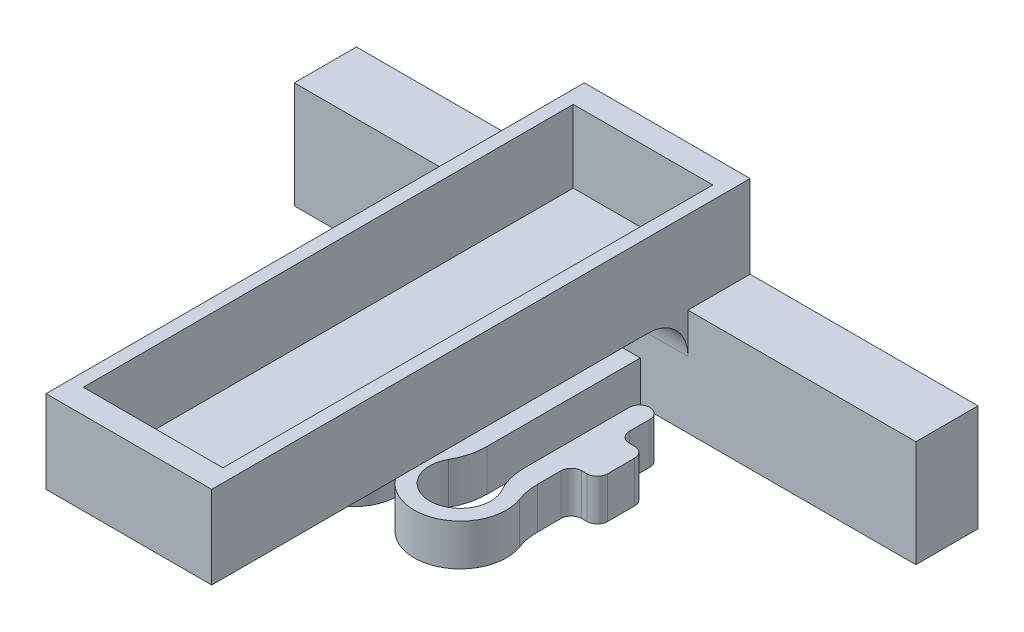
SolidWorks part; units mm, degrees
ref_plane "Front Plane" through (0, 0, 0) normal (0, 0, 1) x (1, 0, 0)
ref_plane "Top Plane" through (0, 0, 0) normal (0, 1, 0) x (1, 0, 0)
ref_plane "Right Plane" through (0, 0, 0) normal (1, 0, 0) x (0, 0, -1)
sketch "Sketch1" plane through (0, 0, 0) normal (0, 1, 0) x (1, 0, 0)
  line L1 (-38.1, 3.81) -> (38.1, 3.81)
  line L2 (-38.1, 3.81) -> (-38.1, -3.81)
  line L3 (-38.1, -3.81) -> (38.1, -3.81)
  line L4 (38.1, 3.81) -> (38.1, -3.81)
  line L5 (-38.1, 3.81) -> (38.1, -3.81) construction
  line L6 (-38.1, -3.81) -> (38.1, 3.81) construction
  point P0 (0, 0)
  dimension "D1" = 7.62
  dimension "D2" = 76.2
extrude "Boss-Extrude1" add sketch "Sketch1" along normal blind 12.7 and the other way blind 0.3649
sketch "Sketch14" plane through (0, 12.7, 0) normal (0, 1, 0) x (1, 0, 0)
  line L0 (-38.1, 3.81) -> (38.1, 3.81) construction
  line L1 (0, 3.81) -> (38.1, 3.81)
  line L2 (0, 3.81) -> (0, -3.81)
  line L3 (0, -3.81) -> (38.1, -3.81)
  line L4 (38.1, 3.81) -> (38.1, -3.81)
  line L5 (38.1, 3.81) -> (38.1, -3.81) construction
  line L6 (-38.1, -3.81) -> (38.1, -3.81) construction
  dimension "D1" = 38.1
extrude "Cut-Extrude5" cut sketch "Sketch14" against normal blind 19.558
sketch "Sketch15" plane through (0, 12.7, 0) normal (0, 1, 0) x (1, 0, 0)
  line L2 (-4.318, -3.81) -> (-1.778, -3.81)
  line L3 (-4.318, -3.81) -> (-4.318, -25.1968)
  line L4 (-4.318, -25.1968) -> (-1.778, -25.1968)
  line L5 (-1.778, -3.81) -> (-1.778, -25.1968)
  line L6 (-11.43, -25.1968) -> (-11.43, -8.4836)
  line L7 (-11.43, -8.4836) -> (-8.89, -8.4836)
  line L8 (-8.89, -8.4836) -> (-8.89, -25.1968)
  line L11 (-11.43, -13.5382) -> (-14.605, -13.5382)
  line L12 (-11.43, -13.5382) -> (-11.43, -19.3802)
  line L13 (-11.43, -19.3802) -> (-14.605, -19.3802)
  line L14 (-14.605, -13.5382) -> (-14.605, -19.3802)
  line L16 (-30.1703, -3.81) -> (0, -3.81) construction
  line L17 (0, 3.81) -> (0, -3.81) construction
  arc A0 (-1.778, -25.1968) -> (-11.43, -25.1968) centre (-6.604, -28.1627) cw
  arc A1 (-8.89, -25.1968) -> (-4.318, -25.1968) centre (-6.604, -28.1627) ccw
  arc A2 (-8.89, -25.1968) -> (0, -3.81) centre (-30.1703, -3.81) cw
  dimension "D1" = 4.6736
  dimension "D2" = 2.54
  dimension "D3" = 2.54
  dimension "D4" = 3.175
  dimension "D5" = 5.842
  dimension "D6" = 21.3868
  dimension "D7" = 9.7282
  dimension "D8" = 1.778
  dimension "D9" = 4.572
extrude "Boss-Extrude2" add sketch "Sketch15" against normal blind 5.08 from offset 8 offset against normal yes
fillet "Fillet1" radius 7.62 4 edges at (-11.43, 2.16, 25.1968) (-1.778, 2.16, 25.1968) (-4.318, 2.16, 25.1968) (-8.89, 2.16, 25.1968)
fillet "Fillet2" radius 1.27 6 edges at (-11.43, 2.16, 19.3802) (-14.605, 2.16, 19.3802) (-14.605, 2.16, 13.5382) (-11.43, 2.16, 13.5382) (-8.89, 2.16, 8.4836) (-11.43, 2.16, 8.4836)
mirror "Mirror1" about plane through (0, -6.858, -3.81) normal (-1, 0, 0) of bodies 117 118
sketch "Sketch17" plane through (0, 4.7, 0) normal (0, 1, 0) x (1, 0, 0)
  line L0 (-1.778, -3.81) -> (-1.778, -23.5177) construction
  line L1 (-1.778, -6.9835) -> (1.778, -6.9835)
  line L2 (-1.778, -6.9835) -> (-1.778, -9.998)
  line L3 (-1.778, -9.998) -> (1.778, -9.998)
  line L4 (1.778, -6.9835) -> (1.778, -9.998)
  line L5 (1.778, -3.81) -> (1.778, -23.5177) construction
  line L7 (-1.778, -17.0862) -> (1.778, -17.0862)
  line L8 (-1.778, -17.0862) -> (-1.778, -20.1007)
  line L9 (-1.778, -20.1007) -> (1.778, -20.1007)
  line L10 (1.778, -17.0862) -> (1.778, -20.1007)
extrude "Boss-Extrude3" add sketch "Sketch17" against normal blind 5.08
sketch "Sketch18" plane through (0, 12.7, 0) normal (0, 1, 0) x (1, 0, 0)
  line L0 (-38.1, 3.81) -> (38.1, 3.81) construction
  line L1 (-10.16, 3.81) -> (10.16, 3.81)
  line L2 (-10.16, 3.81) -> (-10.16, -62.19)
  line L3 (-10.16, -62.19) -> (10.16, -62.19)
  line L4 (10.16, 3.81) -> (10.16, -62.19)
  line L5 (-38.1, -3.81) -> (38.1, -3.81) construction
  point P8 (0, -3.81)
  point P9 (0, 3.81)
  dimension "D1" = 20.32
  dimension "D2" = 66
extrude "Boss-Extrude4" add sketch "Sketch18" along normal blind 10.16
sketch "Sketch19" plane through (0, 22.86, 0) normal (0, 1, 0) x (1, 0, 0)
  line L0 (10.16, 3.81) -> (-10.16, 3.81) construction
  line L1 (-8.5547, -59.2218) -> (8.5547, -59.2218)
  line L2 (-8.5547, -59.2218) -> (-8.5547, 0.8418)
  line L3 (-8.5547, 0.8418) -> (8.5547, 0.8418)
  line L4 (8.5547, -59.2218) -> (8.5547, 0.8418)
  line L5 (-8.5547, -59.2218) -> (8.5547, 0.8418) construction
  line L6 (-8.5547, 0.8418) -> (8.5547, -59.2218) construction
  line L7 (-10.16, 3.81) -> (-10.16, -62.19) construction
  point P0 (0, -29.19)
  point P7 (0, 3.81)
  point P8 (0, -59.2218)
  point P9 (-8.5547, -29.19)
  point P12 (-10.16, -29.19)
extrude "Cut-Extrude14" cut sketch "Sketch19" against normal blind 8.89
fillet "Fillet3" radius 4.92 1 edges at (0, 12.7, 3.81)
